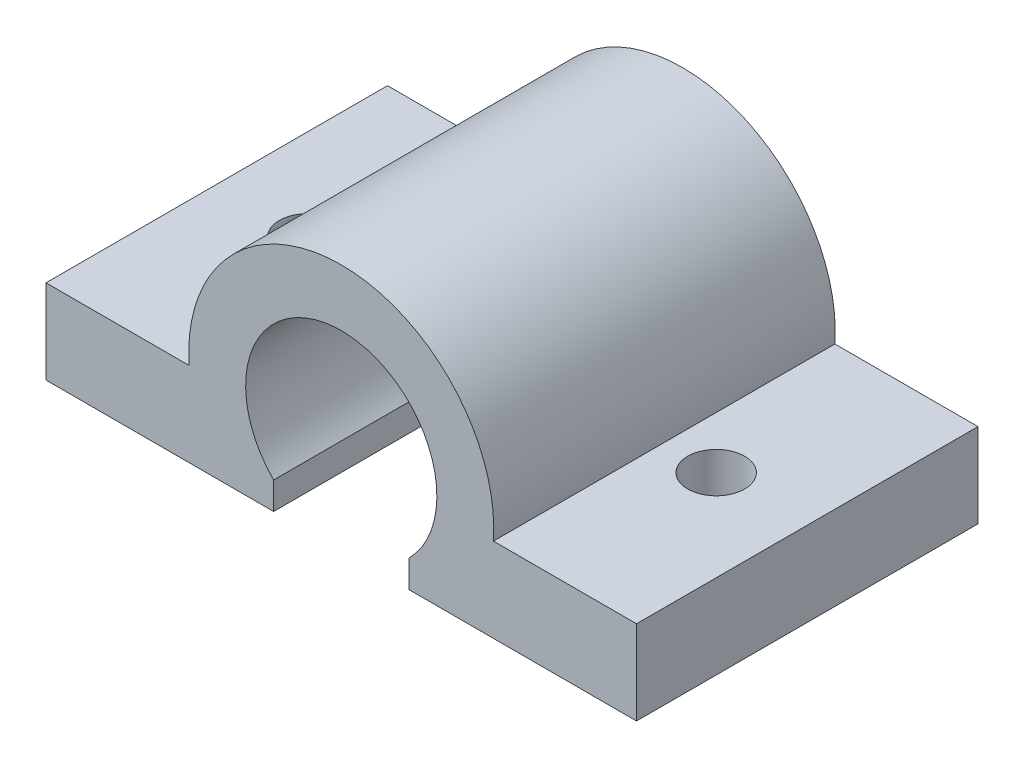
SolidWorks part; units mm, degrees
ref_plane "Front Plane" through (0, 0, 0) normal (0, 0, 1) x (1, 0, 0)
ref_plane "Top Plane" through (0, 0, 0) normal (0, 1, 0) x (1, 0, 0)
ref_plane "Right Plane" through (0, 0, 0) normal (1, 0, 0) x (0, 0, -1)
sketch "Sketch1" plane through (0, 0, 0) normal (0, 0, 1) x (1, 0, 0)
  line L0 (0, 0) -> (-25.4, 0)
  line L1 (15.0868, 0) -> (40.4868, 0)
  line L2 (24.5195, 6.35) -> (40.4868, 6.35)
  line L3 (-9.4327, 6.35) -> (-25.4, 6.35)
  line L4 (-25.4, 6.35) -> (-25.4, 0)
  line L5 (40.4868, 6.35) -> (40.4868, 0)
  arc A0 (0, 0) -> (15.0868, 0) centre (7.5434, 7.5434) cw
  arc A1 (-9.4327, 6.35) -> (24.5195, 6.35) centre (7.5434, 7.5434) cw
  dimension "D2" = 10.668
  dimension "D4" = 15.0868
  dimension "D1" = 25.4
  dimension "D3" = 25.4
  dimension "D5" = 6.35
extrude "Boss-Extrude1" add sketch "Sketch1" along normal blind 38.1
sketch "Sketch2" plane through (0, 6.35, 0) normal (0, 1, 0) x (1, 0, 0)
  line L0 (40.4868, -38.1) -> (40.4868, 0) construction
  line L1 (40.4868, -38.1) -> (24.5195, -38.1) construction
  circle A0 centre (30.3268, -19.05) radius 3.175
  point P4 (0, 0)
  point P7 (0, 0)
  dimension "D3" = 6.35
  dimension "D1" = 10.16
  dimension "D2" = 19.05
extrude "Cut-Extrude1" cut sketch "Sketch2" against normal blind 38.1
sketch "Sketch3" plane through (0, 6.35, 0) normal (0, 1, 0) x (1, 0, 0)
  line L0 (-25.4, -38.1) -> (-25.4, 0) construction
  line L1 (-9.4327, -38.1) -> (-25.4, -38.1) construction
  circle A0 centre (-15.24, -19.05) radius 3.175
  point P2 (0, 0)
  point P5 (0, 0)
  point P6 (0, 0)
  point P8 (-31.5564, -17.0488)
  point P10 (0, 0)
  dimension "D1" = 6.35
  dimension "D2" = 10.16
  dimension "D3" = 19.05
extrude "Cut-Extrude2" cut sketch "Sketch3" against normal through all
sketch "Sketch5" plane through (0, 0, 0) normal (0, 0, -1) x (-1, 0, 0)
  line L0 (-15.0868, 0) -> (-12.0642, 0)
  line L1 (0, 0) -> (-3.0226, 0)
  line L2 (-12.9495, 2.1373) -> (-12.0642, 0)
  line L3 (-2.1373, 2.1373) -> (-3.0226, 0)
  arc A2 (0, 0) -> (-15.0868, 0) centre (-7.5434, 7.5434) ccw
  arc A3 (0, 0) -> (-15.0868, 0) centre (-7.5434, 7.5434) ccw
  arc A4 (-2.1373, 2.1373) -> (-12.9495, 2.1373) centre (-7.5434, 7.5434) ccw
  arc A5 (-2.1373, 2.1373) -> (-12.9495, 2.1373) centre (-7.5434, 7.5434) ccw
  point P6 (0, 0)
  dimension "D3" = 0
  dimension "D1" = 3.0226
  dimension "D2" = 3.0226
  dimension "D4" = 3.0226
sketch "Sketch12" plane through (0, 0, 0) normal (0, -1, 0) x (-1, 0, 0)
  line L1 (25.4, -38.1) -> (0, -38.1)
  line L2 (25.4, -38.1) -> (25.4, 0)
  line L3 (25.4, 0) -> (0, 0)
  line L4 (0, -38.1) -> (0, 0)
  line L5 (-40.4868, -38.1) -> (-15.0868, -38.1)
  line L6 (-40.4868, -38.1) -> (-40.4868, 0)
  line L7 (-40.4868, 0) -> (-15.0868, 0)
  line L8 (-15.0868, -38.1) -> (-15.0868, 0)
  circle A0 centre (15.24, -19.05) radius 3.175
  circle A1 centre (-30.3268, -19.05) radius 3.175
extrude "Boss-Extrude3" add sketch "Sketch12" along normal blind 3.048
extrude "Boss-Extrude4" add sketch "Sketch5" against normal blind 9.525 contours A5 L2 L0 A3 L1 L3
sketch "Sketch14" plane through (0, 0, 9.525) normal (0, 0, 1) x (1, 0, 0)
  line L0 (3.4843, 3.4843) -> (2.1373, 2.1373)
  line L1 (12.9495, 2.1373) -> (11.6025, 3.4843)
  arc A12 (12.9495, 2.1373) -> (2.1373, 2.1373) centre (7.5434, 7.5434) ccw
  arc A13 (12.9495, 2.1373) -> (2.1373, 2.1373) centre (7.5434, 7.5434) ccw
  arc A15 (3.4843, 3.4843) -> (11.6025, 3.4843) centre (7.5434, 7.5434) cw
  dimension "D2" = 0
  dimension "D4" = 5.7404
  dimension "D1" = 1.905
  dimension "D3" = 1.905
  dimension "D5" = 8.1182
extrude "Boss-Extrude5" add sketch "Sketch14" along normal blind 9.525 and the other way blind 9.525 contours A15 L1 A13 L0
